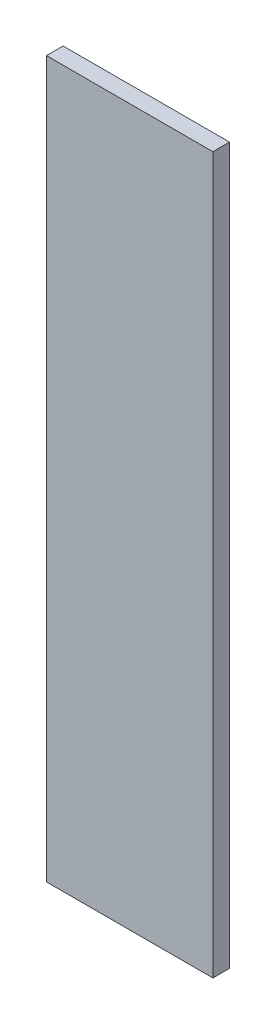
SolidWorks part; units mm, degrees
ref_plane "Front Plane" through (0, 0, 0) normal (0, 0, 1) x (1, 0, 0)
ref_plane "Top Plane" through (0, 0, 0) normal (0, 1, 0) x (1, 0, 0)
ref_plane "Right Plane" through (0, 0, 0) normal (1, 0, 0) x (0, 0, -1)
sketch "Sketch1" plane through (0, 0, 0) normal (0, 0, 1) x (1, 0, 0)
  line L1 (25.4, 222.25) -> (152.4, 222.25)
  line L2 (25.4, 222.25) -> (25.4, -323.85)
  line L3 (25.4, -323.85) -> (152.4, -323.85)
  line L4 (152.4, 222.25) -> (152.4, -323.85)
  dimension "D1" = 546.1
  dimension "D2" = 127
extrude "Boss-Extrude1" add sketch "Sketch1" along normal blind 12.7
